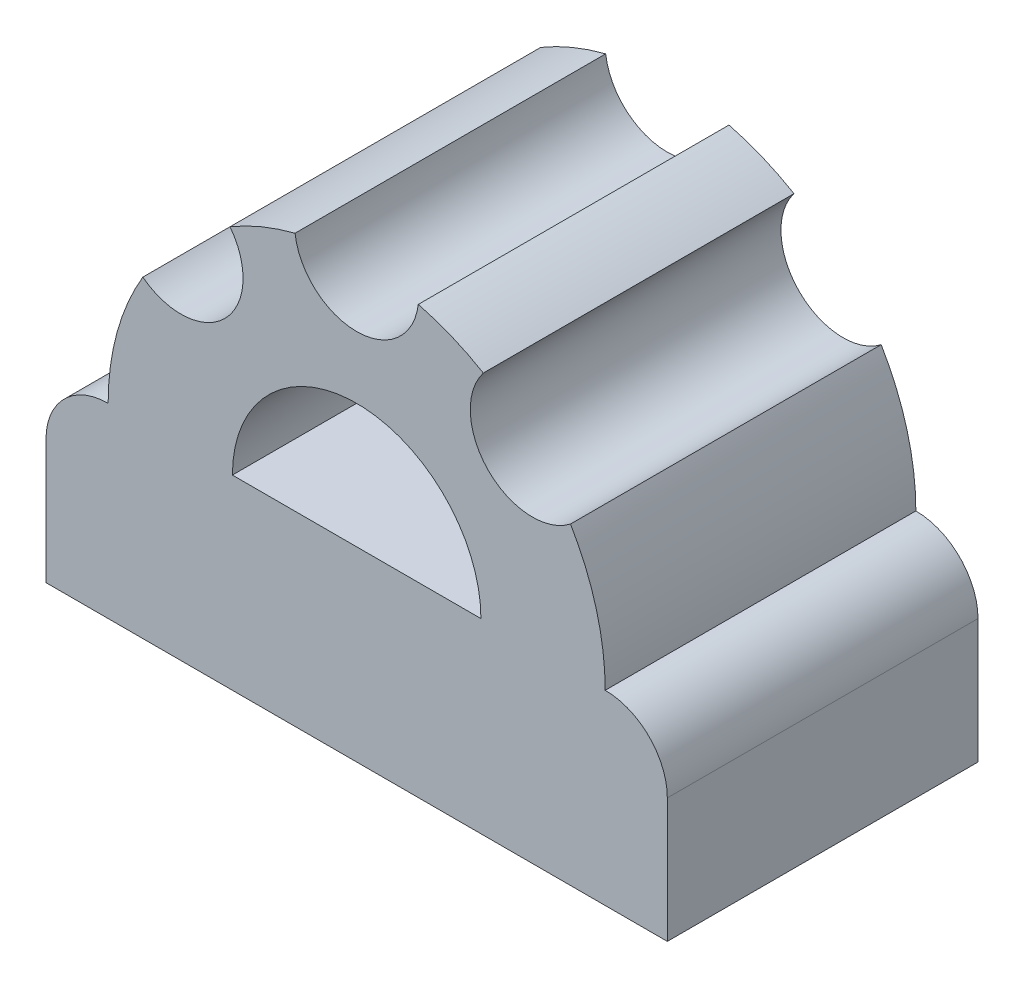
SolidWorks part; units mm, degrees
ref_plane "Front Plane" through (0, 0, 0) normal (0, 0, 1) x (1, 0, 0)
ref_plane "Top Plane" through (0, 0, 0) normal (0, 1, 0) x (1, 0, 0)
ref_plane "Right Plane" through (0, 0, 0) normal (1, 0, 0) x (0, 0, -1)
sketch "Sketch1" plane through (0, 0, 0) normal (0, 0, 1) x (1, 0, 0)
  line L1 (0, 0) -> (-10, 0)
  line L2 (0, 0) -> (0, 3)
  line L3 (0, 3) -> (-10, 3)
  line L4 (-10, 0) -> (-10, 3)
  circle A0 centre (-5, 3) radius 4
  circle A1 centre (-5, 3) radius 2
extrude "Boss-Extrude1" add sketch "Sketch1" along normal blind 5 contours A1 L3 A0 | L3 A1 | A1 L3 A0 L1 | A0 L1 L2 L3 | A0 L3 L4 L1 region at (-0.7616, 1.2717, 0) region at (-5, 0.0854, 0) region at (-9.2384, 1.2717, 0) region at (-2, 3.0894, 0) region at (-5, 2.1512, 0)
sketch "Sketch2" plane through (0, 0, 5) normal (0, 0, 1) x (1, 0, 0)
  circle A0 centre (-5, 7) radius 1
  arc A1 (-1, 3) -> (-9, 3) centre (-5, 3) ccw construction
  circle A2 centre (-2.1716, 5.8284) radius 1
  circle A3 centre (-7.8284, 5.8284) radius 1
extrude "Cut-Extrude1" cut sketch "Sketch2" against normal blind 5 contours A3 | A0 | A2
fillet "Fillet1" radius 1 2 edges at (0, 3, 2.5) (-10, 3, 2.5)
